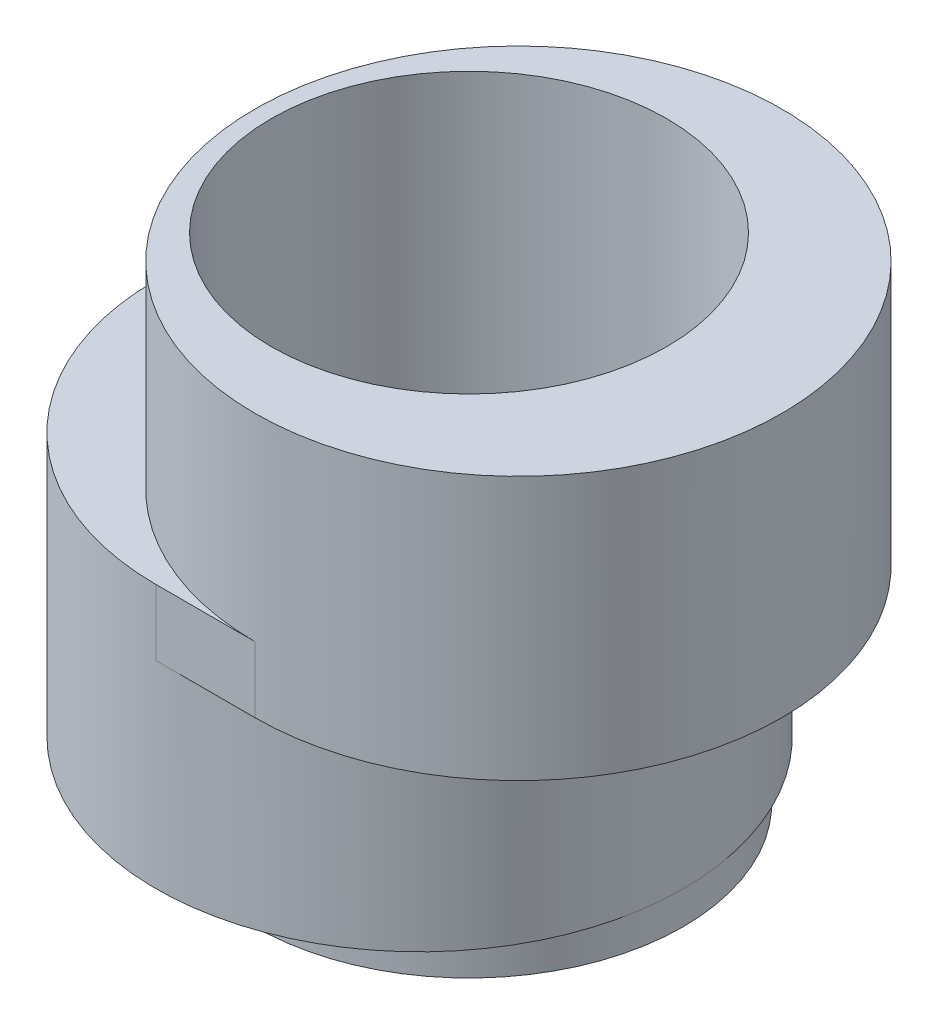
SolidWorks part; units mm, degrees
ref_plane "前视基准面" through (0, 0, 0) normal (0, 0, 1) x (1, 0, 0)
ref_plane "上视基准面" through (0, 0, 0) normal (0, 1, 0) x (1, 0, 0)
ref_plane "右视基准面" through (0, 0, 0) normal (1, 0, 0) x (0, 0, -1)
sketch "草图1" plane through (0, 0, 0) normal (0, 1, 0) x (1, 0, 0)
  line L0 (0, 0) -> (-0.75, 0) construction
  circle A0 centre (0, 0) radius 3
  circle A1 centre (-0.75, 0) radius 4
  dimension "D1" = 0.75
  dimension "D2" = 6
  dimension "D3" = 8
extrude "凸台-拉伸1" add sketch "草图1" along normal blind 3
sketch "草图2" plane through (0, 3, 0) normal (0, 1, 0) x (1, 0, 0)
  line L0 (-0.75, 4) -> (0.75, 4)
  line L1 (-0.75, -4) -> (0.75, -4)
  circle A0 centre (0, 0) radius 3 construction
  circle A1 centre (0, 0) radius 3
  arc A2 (0.75, -4) -> (0.75, 4) centre (0.75, 0) ccw
  circle A3 centre (-0.75, 0) radius 4 construction
  arc A4 (-0.75, 4) -> (-0.75, -4) centre (-0.75, 0) ccw
  dimension "D2" = 8
  dimension "D1" = 0.75
extrude "凸台-拉伸2" add sketch "草图2" along normal blind 1
sketch "草图3" plane through (0, 4, 0) normal (0, 1, 0) x (1, 0, 0)
  circle A0 centre (0.75, 0) radius 4
  circle A1 centre (0, 0) radius 3 construction
  circle A2 centre (0, 0) radius 3
extrude "凸台-拉伸3" add sketch "草图3" along normal blind 3
sketch "草图4" plane through (0, 0, 0) normal (0, -1, 0) x (1, 0, 0)
  circle A0 centre (0, 0) radius 3.25
  circle A1 centre (0, 0) radius 3 construction
  circle A2 centre (0, 0) radius 3
extrude "凸台-拉伸4" add sketch "草图4" along normal blind 0.5
